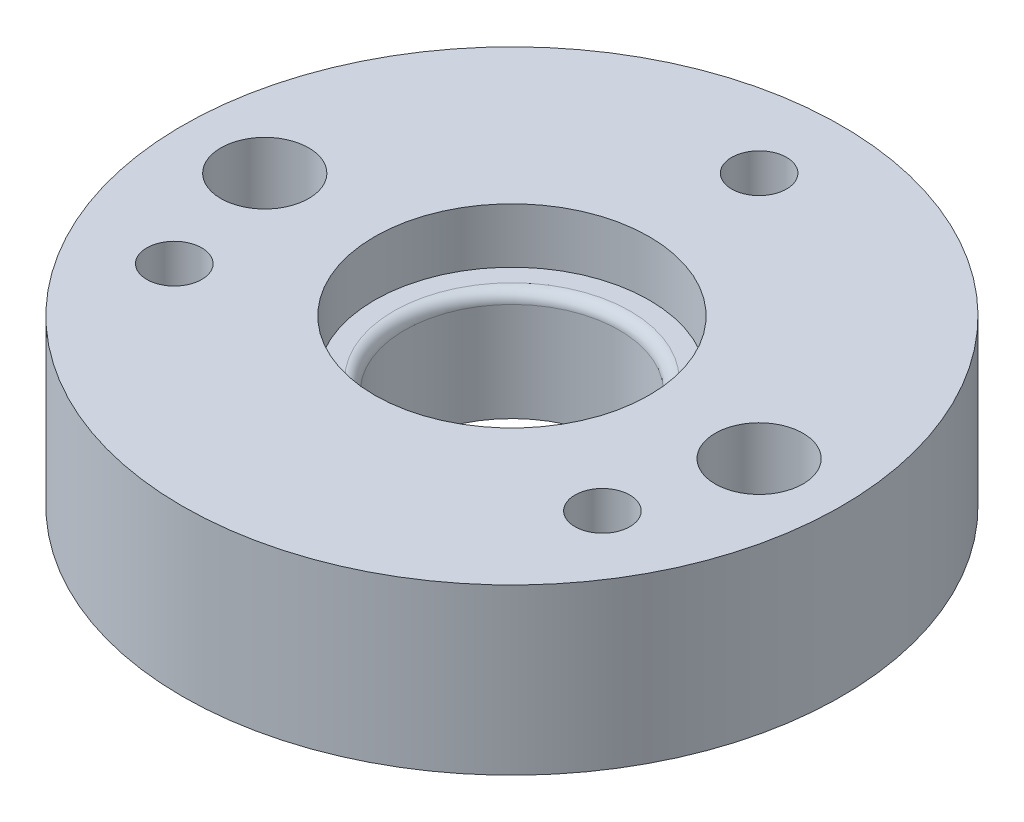
SolidWorks part; units mm, degrees
material "Plain Carbon Steel"
ref_plane "Front Plane" through (0, 0, 0) normal (0, 0, 1) x (1, 0, 0)
ref_plane "Top Plane" through (0, 0, 0) normal (0, 1, 0) x (1, 0, 0)
ref_plane "Right Plane" through (0, 0, 0) normal (1, 0, 0) x (0, 0, -1)
sketch "Sketch1" plane through (0, 0, 0) normal (0, 1, 0) x (1, 0, 0)
  circle A0 centre (0, 0) radius 30
  dimension "D1" = 60
extrude "Boss-Extrude1" add sketch "Sketch1" along normal blind 15
sketch "Sketch2" plane through (0, 15, 0) normal (0, 1, 0) x (1, 0, 0)
  circle A0 centre (0, 0) radius 9.765
  dimension "D1" = 19.53
extrude "Cut-Extrude1" cut sketch "Sketch2" against normal up to next
sketch "Sketch3" plane through (0, 15, 0) normal (0, 1, 0) x (1, 0, 0)
  circle A0 centre (0, 0) radius 12.5
  dimension "D1" = 25
extrude "Cut-Extrude2" cut sketch "Sketch3" against normal blind 5
fillet "Fillet1" radius 1 1 edges at (0, 10, 9.765)
hole_wizard "M6 Tapped Hole1" positions "Sketch8" profile "Sketch7" tap size "M6" standard "ISO"
sketch "Sketch8" plane through (0, 15, 0) normal (0, 1, 0) x (1, 0, 0)
  line L0 (0, 0) -> (-19.4856, -11.25) construction
  line L2 (0, 0) -> (19.4856, -11.25) construction
  line L4 (0, 0) -> (0, 22.5) construction
  circle A0 centre (0, 0) radius 22.5 construction
  point P0 (0, 22.5)
  point P2 (19.4856, -11.25)
  point P4 (-19.4856, -11.25)
  dimension "D1" = 45
  dimension "D2" = 120
  dimension "D3" = 120
sketch "Sketch7" plane through (0, 15, -22.5) normal (1, 0, 0) x (0, 0, 1)
  line L0 (0, 0) -> (0, 18.5022)
  line L1 (0, 18.5022) -> (2.5, 17)
  line L2 (2.5, 17) -> (2.5, 0)
  line L5 (2.5, 0) -> (0, 0)
  line L10 (0, 18.5022) -> (-2.5, 17) construction
  line L11 (0, -6.35) -> (0, 107.95) construction
  dimension "Tap Drill Dia." = 5
  dimension "Tap Drill Depth" = 17
  dimension "Drill Angle" = 118
cosmetic thread "Hole Thread1"
cosmetic thread "Hole Thread2"
cosmetic thread "Hole Thread3"
hole_wizard "Ø8.0mm Dowel Hole1" positions "Sketch11" profile "Sketch10" hole size "Ø8.0" standard "ISO" end condition through all
sketch "Sketch11" plane through (0, 15, 0) normal (0, 1, 0) x (1, 0, 0)
  circle A0 centre (0, 0) radius 22.5 construction
  point P0 (22.5, 0)
  point P2 (-22.5, 0)
  dimension "D1" = 45
sketch "Sketch10" plane through (22.5, 15, 0) normal (1, 0, 0) x (0, 0, 1)
  line L0 (0, 0) -> (0, 15)
  line L1 (0, 15) -> (4, 15)
  line L2 (4, 15) -> (4, 0)
  line L5 (4, 0) -> (0, 0)
  line L11 (0, -6.35) -> (0, 107.95) construction
  dimension "Thru Hole Dia." = 8
  dimension "Thru Hole Depth" = 15
